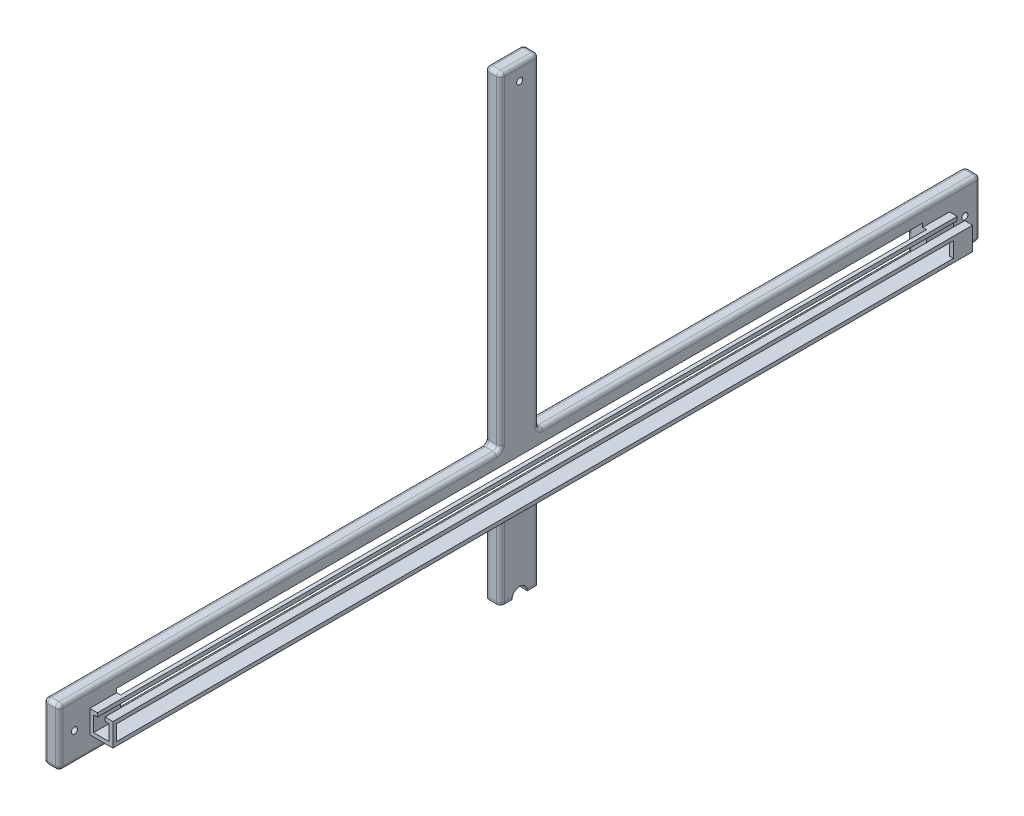
SolidWorks part; units mm, degrees
ref_plane "Front Plane" through (0, 0, 0) normal (0, 0, 1) x (1, 0, 0)
ref_plane "Top Plane" through (0, 0, 0) normal (0, 1, 0) x (1, 0, 0)
ref_plane "Right Plane" through (0, 0, 0) normal (1, 0, 0) x (0, 0, -1)
sketch "Sketch3" plane through (0, 0, 0) normal (1, 0, 0) x (0, 0, -1)
  line L0 (-151.0311, 38.4862) -> (-36.0311, 38.4862)
  line L5 (-276.0311, 38.4862) -> (-161.0311, 38.4862)
  line L6 (-276.0311, 38.4862) -> (-276.0311, 23.4862)
  line L7 (-276.0311, 23.4862) -> (-161.0311, 23.4862)
  line L8 (-36.0311, 38.4862) -> (-36.0311, 23.4862)
  line L9 (-161.0311, 123.4862) -> (-151.0311, 123.4862)
  line L10 (-161.0311, 123.4862) -> (-161.0311, 38.4862)
  line L12 (-151.0311, 123.4862) -> (-151.0311, 38.4862)
  line L13 (-151.0311, 23.4862) -> (-36.0311, 23.4862)
  line L14 (-161.0311, 23.4862) -> (-161.0311, 3.4862)
  line L15 (-151.0311, 23.4862) -> (-151.0311, 3.4862)
  line L20 (-398.8778, 3.4862) -> (82.314, 3.4862) construction
  line L21 (-161.0311, 3.4862) -> (-151.0311, 3.4862)
  circle A2 centre (-156.0311, 138.4862) radius 0.8
  dimension "D2" = 240
  dimension "D3" = 20
  dimension "D4" = 10
  dimension "D6" = 15
  dimension "D8" = 85
  dimension "D10" = 115
  dimension "D16" = 120
extrude "Boss-Extrude1" add sketch "Sketch3" along normal blind 4 contours L12 L0 L8 L13 L15 L21 L14 L7 L6 L5 L10 L9
sketch "Sketch4" plane through (0, 0, 0) normal (1, 0, 0) x (0, 0, -1)
  line L2 (-316.8277, 3.4862) -> (27.7287, 3.4862) construction
  line L3 (-161.0311, 123.4862) -> (-151.0311, 123.4862) construction
  line L4 (-276.0311, 38.4862) -> (-276.0311, 23.4862) construction
  line L8 (-276.0311, 23.4862) -> (-161.0311, 23.4862) construction
  line L9 (-276.0311, 38.4862) -> (-161.0311, 38.4862) construction
  line L10 (-151.0311, 123.4862) -> (-151.0311, 38.4862) construction
  line L13 (-36.0311, 38.4862) -> (-36.0311, 23.4862) construction
  line L14 (-151.0311, 23.4862) -> (-36.0311, 23.4862) construction
  line L15 (-161.0311, 123.4862) -> (-161.0311, 38.4862) construction
  circle A1 centre (-156.0311, 119.4862) radius 0.8
  circle A3 centre (-272.0311, 30.9862) radius 0.8
  circle A5 centre (-40.0311, 30.9862) radius 0.8
  circle A7 centre (-156.0311, 30.9862) radius 2
  point P10 (-156.0311, 123.4862)
  dimension "D1" = 1.6
  dimension "D3" = 7.5
  dimension "D6" = 1.6
  dimension "D8" = 4
  dimension "D9" = 4
  dimension "D10" = 7.5
  dimension "D11" = 1.6
  dimension "D12" = 4
  dimension "D2" = 4
  dimension "D4" = 120
  dimension "D5" = 7.5
  dimension "D7" = 5
  dimension "D13" = 7.5
  dimension "D14" = 5
extrude "Cut-Extrude1" cut sketch "Sketch4" against normal blind 4 and the other way blind 4
fillet "Fillet1" radius 1 32 edges at (2, 123.4862, 161.0311) (2, 38.4862, 161.0311) (2, 38.4862, 276.0311) (2, 23.4862, 276.0311) (2, 23.4862, 161.0311) (2, 23.4862, 151.0311) (2, 23.4862, 36.0311) (2, 38.4862, 36.0311) (2, 38.4862, 151.0311) (2, 123.4862, 151.0311) (4, 80.9862, 161.0311) (4, 38.4862, 218.5311) (4, 30.9862, 276.0311) (4, 23.4862, 218.5311) (4, 13.4862, 161.0311) (4, 13.4862, 151.0311) (4, 23.4862, 93.5311) (4, 30.9862, 36.0311) (4, 38.4862, 93.5311) (4, 80.9862, 151.0311) (4, 123.4862, 156.0311) (0, 80.9862, 161.0311) (0, 38.4862, 218.5311) (0, 30.9862, 276.0311) (0, 23.4862, 218.5311) (0, 13.4862, 161.0311) (0, 13.4862, 151.0311) (0, 23.4862, 93.5311) (0, 30.9862, 36.0311) (0, 38.4862, 93.5311) (0, 80.9862, 151.0311) (0, 123.4862, 156.0311)
ref_plane "Plane1" through (4, 0, 0) normal (1, 0, 0) x (0, 0, -1)
ref_plane "Plane2" through (0, 0, 268.0311) normal (0, 0, 1) x (1, 0, 0)
sketch "Sketch6" plane through (0, 0, 268.0311) normal (0, 0, 1) x (1, 0, 0)
  line L0 (4, 37.4862) -> (4, 24.4862) construction
  line L1 (5, 28.9862) -> (9, 28.9862)
  line L3 (4, 27.9862) -> (10, 27.9862)
  line L4 (10, 33.9862) -> (10, 27.9862)
  line L6 (4, 33.9862) -> (4, 27.9862)
  line L9 (4, 27.9862) -> (4.9389, 27.9862)
  line L10 (5, 32.9862) -> (5, 28.9862)
  line L11 (4, 33.9862) -> (6, 33.9862)
  line L13 (5, 32.9862) -> (6, 32.9862)
  line L14 (6, 33.9862) -> (6, 32.9862)
  line L15 (7.9831, 34.0232) -> (9.9831, 34.0232)
  line L16 (7.9831, 34.0232) -> (7.9831, 32.9862)
  line L17 (7.9831, 32.9862) -> (9, 32.9862)
  line L19 (9, 34.0232) -> (9.9831, 34.0232)
  line L20 (9, 32.9862) -> (9, 28.9862)
  line L21 (10.0937, 27.9862) -> (10, 27.9862)
  line L23 (3, 23.4862) -> (1, 23.4862) construction
  line L24 (1, 38.4862) -> (3, 38.4862) construction
  point P23 (2, 23.4862)
  dimension "D1" = 4
  dimension "D2" = 4
  dimension "D3" = 4
  dimension "D4" = 1
  dimension "D5" = 6
  dimension "D6" = 6
  dimension "D7" = 6
  dimension "D8" = 2
  dimension "D9" = 2
  dimension "D10" = 1
  dimension "D11" = 1
  dimension "D12" = 1.0169
  dimension "D13" = 4.5
  dimension "D14" = 4.5
  dimension "D15" = 6
sketch "Sketch7" plane through (0, 0, 268.0311) normal (0, 0, 1) x (1, 0, 0)
  line L0 (6, 33.9862) -> (6, 32.9862)
  line L1 (6, 32.9862) -> (5, 32.9862)
  line L2 (5, 32.9862) -> (5, 28.9862)
  line L3 (5, 28.9862) -> (9, 28.9862)
  line L4 (9, 28.9862) -> (9, 32.9862)
  line L5 (9, 32.9862) -> (7.9831, 32.9862)
  line L6 (7.9831, 32.9862) -> (7.9831, 34.0232)
  line L7 (7.9831, 34.0232) -> (10, 33.9862)
  line L8 (10, 33.9862) -> (10, 27.9862)
  line L9 (10, 27.9862) -> (4, 27.9862)
  line L10 (4, 27.9862) -> (4, 33.9862)
  line L11 (4, 33.9862) -> (6, 33.9862)
extrude "Boss-Extrude5" add sketch "Sketch7" against normal blind 224
ref_plane "Plane3" through (10, 0, 0) normal (1, 0, 0) x (0, 0, -1)
sketch "Sketch9" plane through (10, 0, 0) normal (1, 0, 0) x (0, 0, -1)
  line L0 (-44.0311, 27.9862) -> (-268.0311, 27.9862) construction
  line L1 (-267.0311, 32.9862) -> (-49.0311, 32.9862)
  line L2 (-267.0311, 32.9862) -> (-267.0311, 28.9862)
  line L3 (-267.0311, 28.9862) -> (-49.0311, 28.9862)
  line L4 (-49.0311, 32.9862) -> (-49.0311, 28.9862)
  line L5 (-268.0311, 32.9862) -> (-268.0311, 28.9862) construction
  line L6 (-44.0311, 27.9862) -> (-44.0311, 33.9862) construction
  dimension "D1" = 4
  dimension "D2" = 1
  dimension "D3" = 1
  dimension "D4" = 218
  dimension "D5" = 5
extrude "Cut-Extrude2" cut sketch "Sketch9" against normal blind 2
sketch "Sketch10" plane through (4, 0, 0) normal (1, 0, 0) x (0, 0, -1)
  line L0 (-257.3659, 3.9862) -> (-36.5246, 3.9862) construction
  line L1 (-150.0311, 24.4862) -> (-37.0311, 24.4862) construction
  line L2 (-150.0311, 3.4862) -> (-37.0311, 3.4862) construction
  dimension "D1" = 20.5
  dimension "D2" = 0.5
ref_plane "Plane5" through (0, 3.9862, 0) normal (0, -1, 0) x (0, 0, -1)
split "Split1" trim tools "Plane5" bodies to split 106 resulting bodies 111 112
ref_plane "Plane16" through (0, 0, 0) normal (-1, 0, 0) x (0, 0, 1)
sketch "Sketch11" plane through (0, 0, 0) normal (-1, 0, 0) x (0, 0, 1)
  line L0 (36.0311, 24.4862) -> (36.0311, 37.4862) construction
  line L1 (51.0311, 34.9862) -> (261.0311, 34.9862)
  line L2 (51.0311, 34.9862) -> (51.0311, 26.9862)
  line L3 (51.0311, 26.9862) -> (261.0311, 26.9862)
  line L4 (261.0311, 34.9862) -> (261.0311, 26.9862)
  line L5 (150.0311, 23.4862) -> (37.0311, 23.4862) construction
  line L6 (37.0311, 38.4862) -> (150.0311, 38.4862) construction
  line L7 (276.0311, 37.4862) -> (276.0311, 24.4862) construction
  dimension "D1" = 15
  dimension "D2" = 8
  dimension "D3" = 3.5
  dimension "D4" = 3.5
  dimension "D5" = 15
extrude "Cut-Extrude3" cut sketch "Sketch11" against normal blind 5
fillet "Fillet4" radius 1 4 edges at (0, 30.9862, 261.0311) (0, 26.9862, 156.0311) (0, 34.9862, 156.0311) (0, 30.9862, 51.0311)
sketch "Sketch12" plane through (0, 0, 0) normal (-1, 0, 0) x (0, 0, 1)
  line L0 (160.0311, 3.4862) -> (152.0311, 3.4862) construction
  line L1 (151.0311, 3.9862) -> (151.0311, 22.4862) construction
  circle A0 centre (156.0311, 3.4862) radius 2
  dimension "D1" = 5
extrude "Cut-Extrude4" cut sketch "Sketch12" against normal blind 5
